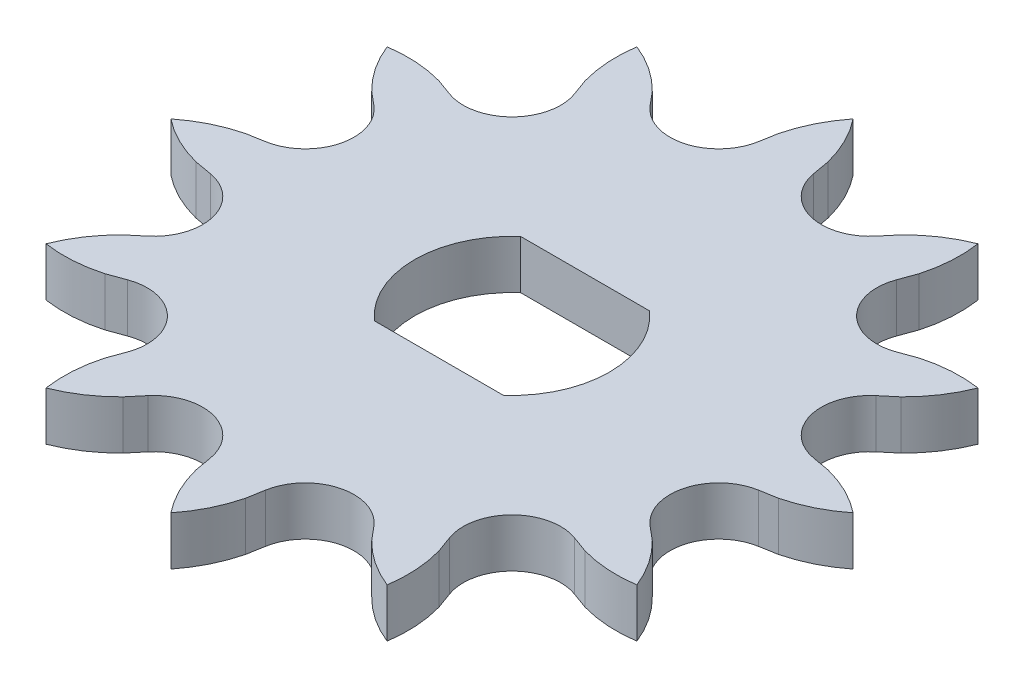
SolidWorks part; units mm, degrees
note: The reader was unsure of these and kept them because the rebuilt part matched: shared geometry of "Sketch2<5>".
ref_plane "Front Plane" through (0, 0, 0) normal (0, 0, 1) x (1, 0, 0)
ref_plane "Top Plane" through (0, 0, 0) normal (0, 1, 0) x (1, 0, 0)
ref_plane "Right Plane" through (0, 0, 0) normal (1, 0, 0) x (0, 0, -1)
sketch "Sketch1" plane through (0, 0, 0) normal (0, 1, 0) x (1, 0, 0)
  line L0 (0, 0) -> (0, 14) construction
  line L1 (0, 0) -> (-14, 0) construction
  line L2 (0, 0) -> (3.0919, 11.5948) construction
  line L3 (0, 0) -> (-3.0919, 11.5948) construction
  line L4 (-4.627, 10.313) -> (-5.0898, 10.8671)
  line L7 (-1.1222, 11.2475) -> (-0.9969, 11.9585)
  circle A0 centre (0, 0) radius 14
  circle A1 centre (0, 0) radius 10
  circle A2 centre (0, 0) radius 12 construction
  circle A3 centre (0, 0) radius 11.5 construction
  arc A6 (-4.627, 10.313) -> (-1.1222, 11.2475) centre (-3.0919, 11.5948) ccw
  conic Q0 (-0.9969, 11.9585) -> (0, 14) control (-0.371, 14) rho 0.627845
  conic Q1 (-5.0898, 10.8671) -> (-6.9708, 12.1412) control (-6.649, 12.3259) rho 0.627845
  dimension "D1" = 28
  dimension "D2" = 20
  dimension "D3" = 24
  dimension "D4" = 23
extrude "Boss-Extrude3" add sketch "Sketch1" along normal blind 2 contours L4 Q1 A0 Q0 L7 A6 A1 | A1 | Q1 L4 A6 L7 Q0 A0
sketch "Sketch2" plane through (0, 2, 0) normal (0, 1, 0) x (1, 0, 0)
  line L0 (0, 0) -> (0, 14) construction
  line L1 (0, 0) -> (3.6235, 13.523) construction
  line L2 (0, 0) -> (-3.6235, 13.523) construction
  line L3 (-1.0104, 11.9574) -> (-1.1362, 11.2438)
  line L4 (5.1037, 10.8606) -> (4.6379, 10.3055)
  line L5 (-1.881, 7.02) -> (-1.8257, 6.954)
  line L6 (-1.881, 7.02) -> (-1.8959, 6.9352)
  line L7 (-5.1037, 10.8606) -> (-4.6379, 10.3055)
  line L8 (1.0104, 11.9574) -> (1.1362, 11.2438)
  line L9 (9.8502, 6.8537) -> (9.1693, 6.6059)
  line L10 (6.8537, 9.8502) -> (6.6059, 9.1693)
  line L11 (11.9574, 1.0104) -> (11.2438, 1.1362)
  line L12 (10.8606, 5.1037) -> (10.3055, 4.6379)
  line L13 (10.8606, -5.1037) -> (10.3055, -4.6379)
  line L14 (11.9574, -1.0104) -> (11.2438, -1.1362)
  line L15 (6.8537, -9.8502) -> (6.6059, -9.1693)
  line L16 (9.8502, -6.8537) -> (9.1693, -6.6059)
  line L17 (1.0104, -11.9574) -> (1.1362, -11.2438)
  line L18 (5.1037, -10.8606) -> (4.6379, -10.3055)
  line L19 (-5.1037, -10.8606) -> (-4.6379, -10.3055)
  line L20 (-1.0104, -11.9574) -> (-1.1362, -11.2438)
  line L21 (-9.8502, -6.8537) -> (-9.1693, -6.6059)
  line L22 (-6.8537, -9.8502) -> (-6.6059, -9.1693)
  line L23 (-11.9574, -1.0104) -> (-11.2438, -1.1362)
  line L24 (-10.8606, -5.1037) -> (-10.3055, -4.6379)
  line L25 (-10.8606, 5.1037) -> (-10.3055, 4.6379)
  line L26 (-11.9574, 1.0104) -> (-11.2438, 1.1362)
  line L27 (-6.8537, 9.8502) -> (-6.6059, 9.1693)
  line L28 (-9.8502, 6.8537) -> (-9.1693, 6.6059)
  line L29 (0, 0) -> (-1.1362, 11.2438) construction
  circle A1 centre (0, 0) radius 11.5 construction
  circle A2 centre (0, 0) radius 10 construction
  circle A3 centre (0, 0) radius 12 construction
  arc A6 (-1.0104, 11.9574) -> (0, 14) centre (4.2499, 10.6266) cw
  arc A7 (-1.1362, 11.2438) -> (-4.6379, 10.3055) centre (-3.1058, 11.5911) cw
  arc A8 (-5.1037, 10.8606) -> (-7, 12.1244) centre (-8.9938, 7.078) ccw
  arc A10 (4.6379, 10.3055) -> (1.1362, 11.2438) centre (3.1058, 11.5911) cw
  arc A11 (5.1037, 10.8606) -> (7, 12.1244) centre (8.9938, 7.078) cw
  arc A12 (1.0104, 11.9574) -> (0, 14) centre (-4.2499, 10.6266) ccw
  arc A13 (9.1693, 6.6059) -> (6.6059, 9.1693) centre (8.4853, 8.4853) cw
  arc A14 (9.8502, 6.8537) -> (12.1244, 7) centre (11.3278, 1.6328) cw
  arc A15 (6.8537, 9.8502) -> (7, 12.1244) centre (1.6328, 11.3278) ccw
  arc A16 (11.2438, 1.1362) -> (10.3055, 4.6379) centre (11.5911, 3.1058) cw
  arc A17 (11.9574, 1.0104) -> (14, 0) centre (10.6266, -4.2499) cw
  arc A18 (10.8606, 5.1037) -> (12.1244, 7) centre (7.078, 8.9938) ccw
  arc A19 (10.3055, -4.6379) -> (11.2438, -1.1362) centre (11.5911, -3.1058) cw
  arc A20 (10.8606, -5.1037) -> (12.1244, -7) centre (7.078, -8.9938) cw
  arc A21 (11.9574, -1.0104) -> (14, 0) centre (10.6266, 4.2499) ccw
  arc A22 (6.6059, -9.1693) -> (9.1693, -6.6059) centre (8.4853, -8.4853) cw
  arc A23 (6.8537, -9.8502) -> (7, -12.1244) centre (1.6328, -11.3278) cw
  arc A24 (9.8502, -6.8537) -> (12.1244, -7) centre (11.3278, -1.6328) ccw
  arc A25 (1.1362, -11.2438) -> (4.6379, -10.3055) centre (3.1058, -11.5911) cw
  arc A26 (1.0104, -11.9574) -> (0, -14) centre (-4.2499, -10.6266) cw
  arc A27 (5.1037, -10.8606) -> (7, -12.1244) centre (8.9938, -7.078) ccw
  arc A28 (-4.6379, -10.3055) -> (-1.1362, -11.2438) centre (-3.1058, -11.5911) cw
  arc A29 (-5.1037, -10.8606) -> (-7, -12.1244) centre (-8.9938, -7.078) cw
  arc A30 (-1.0104, -11.9574) -> (0, -14) centre (4.2499, -10.6266) ccw
  arc A31 (-9.1693, -6.6059) -> (-6.6059, -9.1693) centre (-8.4853, -8.4853) cw
  arc A32 (-9.8502, -6.8537) -> (-12.1244, -7) centre (-11.3278, -1.6328) cw
  arc A33 (-6.8537, -9.8502) -> (-7, -12.1244) centre (-1.6328, -11.3278) ccw
  arc A34 (-11.2438, -1.1362) -> (-10.3055, -4.6379) centre (-11.5911, -3.1058) cw
  arc A35 (-11.9574, -1.0104) -> (-14, 0) centre (-10.6266, 4.2499) cw
  arc A36 (-10.8606, -5.1037) -> (-12.1244, -7) centre (-7.078, -8.9938) ccw
  arc A37 (-10.3055, 4.6379) -> (-11.2438, 1.1362) centre (-11.5911, 3.1058) cw
  arc A38 (-10.8606, 5.1037) -> (-12.1244, 7) centre (-7.078, 8.9938) cw
  arc A39 (-11.9574, 1.0104) -> (-14, 0) centre (-10.6266, -4.2499) ccw
  arc A40 (-6.6059, 9.1693) -> (-9.1693, 6.6059) centre (-8.4853, 8.4853) cw
  arc A41 (-6.8537, 9.8502) -> (-7, 12.1244) centre (-1.6328, 11.3278) cw
  arc A42 (-9.8502, 6.8537) -> (-12.1244, 7) centre (-11.3278, 1.6328) ccw
  dimension "D2" = 20
  dimension "D3" = 23
  dimension "D4" = 24
  dimension "D5" = 15
  dimension "D7" = 11.3011
  dimension "D6" = 15
  dimension "D8" = 10
extrude "Cut-Extrude4" cut sketch "Sketch2" against normal blind 2
sketch "Sketch3" plane through (0, 2, 0) normal (0, 1, 0) x (1, 0, 0)
  line L0 (0, -3) -> (0, 3) construction
  line L1 (-2.6458, 3) -> (2.6458, 3)
  line L2 (-2.6458, -3) -> (2.6458, -3)
  arc A0 (2.6458, -3) -> (2.6458, 3) centre (0, 0) ccw
  arc A1 (-2.6458, 3) -> (-2.6458, -3) centre (0, 0) ccw
  point P7 (0, 0)
  point P10 (0, 3)
  point P13 (0, -3)
  dimension "D1" = 8
  dimension "D2" = 6
extrude "Cut-Extrude5" cut sketch "Sketch3" against normal blind 2
sketch "Sketch4" plane through (0, 2, 0) normal (0, 1, 0) x (1, 0, 0)
  point P0 (0, 0)
extrude "Cut-Extrude7" cut sketch "Sketch2<5>" against normal blind 2 contours A42 L28 A40 L27 A41 L5 | A39 L26 A37 L25 A38 L5 | A36 L24 A34 L23 A35 L5 | A33 L22 A31 L21 A32 L5 | A30 L20 A28 L19 A29 L5 | A27 L18 A25 L17 A26 L5 | A24 L16 A22 L15 A23 L5 | A21 L14 A19 L13 A20 L5 | A18 L12 A16 L11 A17 L5 | A15 L10 A13 L9 A14 L5 | A12 L8 A10 L4 A11 L5
sketch "Sketch2<5>" plane through (0, 2, 0) normal (0, 1, 0) x (1, 0, 0) same geometry as "Sketch2"
